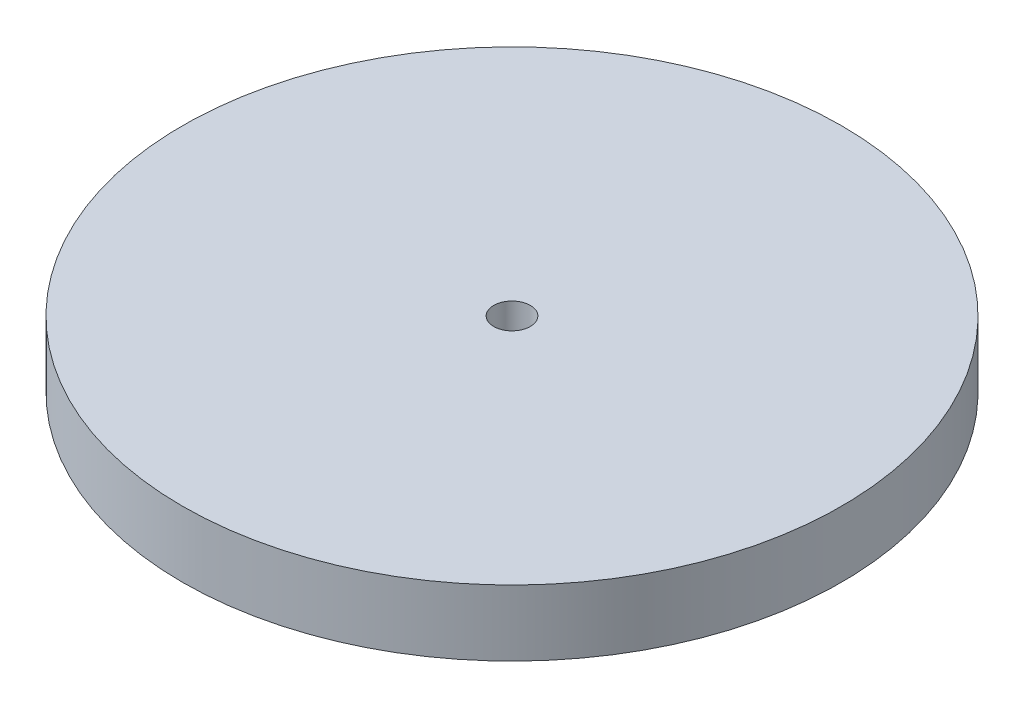
SolidWorks part; units mm, degrees
ref_plane "Front Plane" through (0, 0, 0) normal (0, 0, 1) x (1, 0, 0)
ref_plane "Top Plane" through (0, 0, 0) normal (0, 1, 0) x (1, 0, 0)
ref_plane "Right Plane" through (0, 0, 0) normal (1, 0, 0) x (0, 0, -1)
sketch "Sketch1" plane through (0, 0, 0) normal (0, 1, 0) x (1, 0, 0)
  circle A2 centre (-14.7269, 0) radius 45
  circle A3 centre (-14.7269, 0) radius 2.5
  point P1 (-14.7269, 0)
  dimension "D3" = 90
  dimension "D1" = 5
extrude "Boss-Extrude1" add sketch "Sketch1" along normal blind 9
